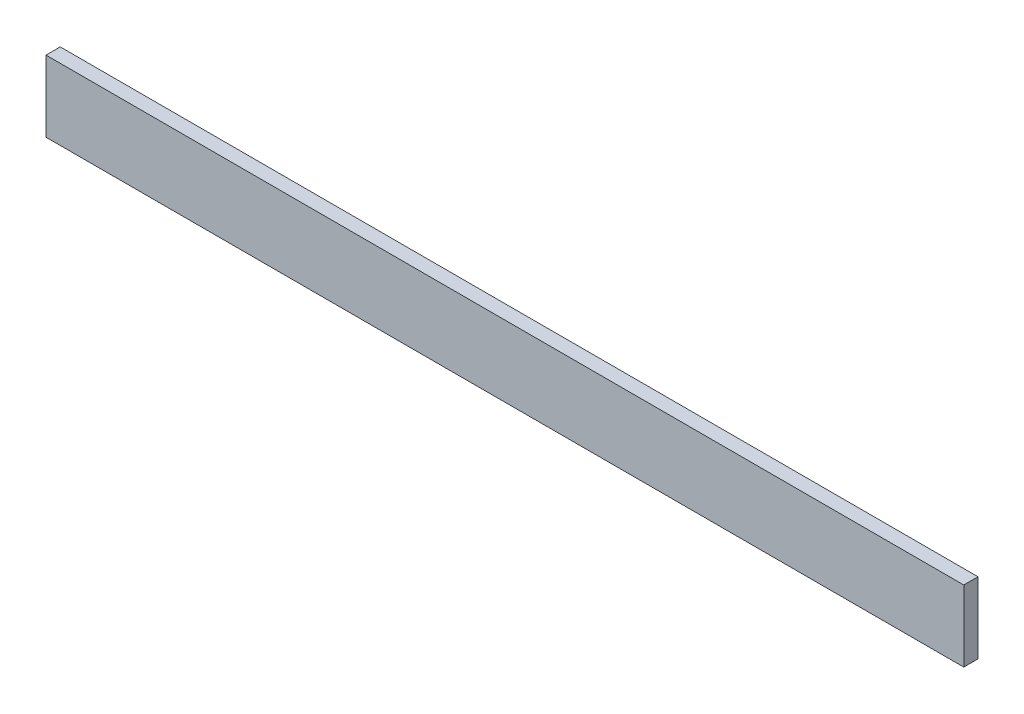
SolidWorks part; units mm, degrees
ref_plane "Plano frontal" through (0, 0, 0) normal (0, 0, 1) x (1, 0, 0)
ref_plane "Plano superior" through (0, 0, 0) normal (0, 1, 0) x (1, 0, 0)
ref_plane "Plano direito" through (0, 0, 0) normal (1, 0, 0) x (0, 0, -1)
sketch "Esboço1" plane through (0, 0, 0) normal (0, 0, 1) x (1, 0, 0)
  line L1 (-72.1079, 0) -> (56.8921, 0)
  line L2 (-72.1079, 0) -> (-72.1079, -10)
  line L3 (-72.1079, -10) -> (56.8921, -10)
  line L4 (56.8921, 0) -> (56.8921, -10)
  dimension "D1" = 129
  dimension "D2" = 10
extrude "Ressalto-extrusão1" add sketch "Esboço1" along normal blind 2
